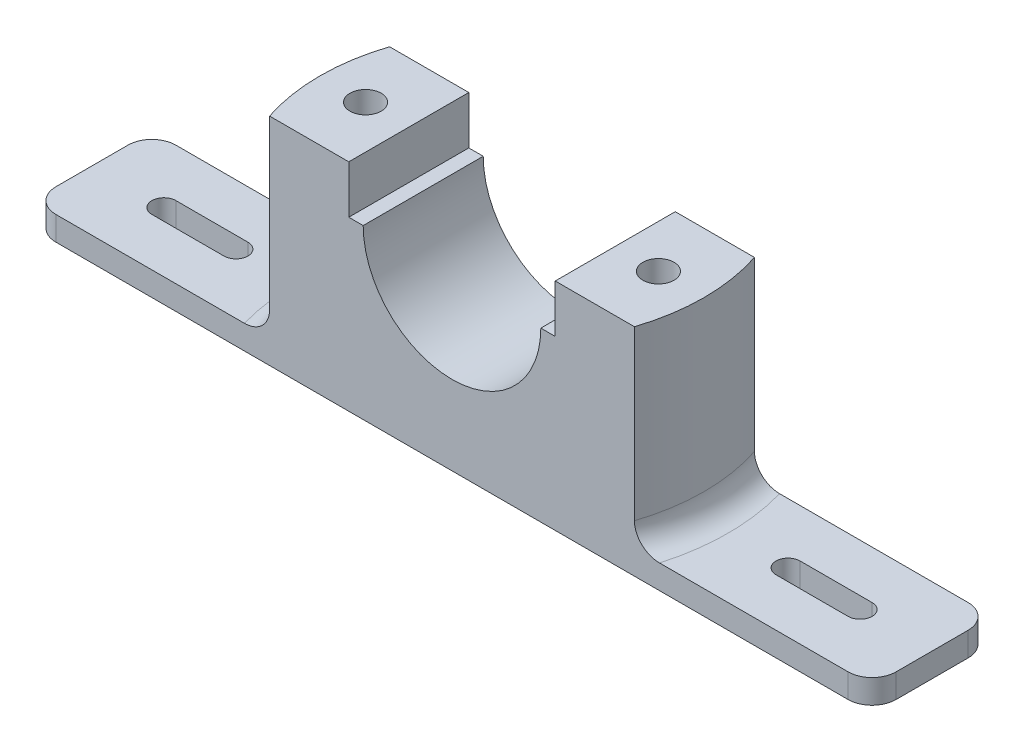
SolidWorks part; units mm, degrees
material "Plain Carbon Steel"
ref_plane "Front Plane" through (0, 0, 0) normal (0, 0, 1) x (1, 0, 0)
ref_plane "Top Plane" through (0, 0, 0) normal (0, 1, 0) x (1, 0, 0)
ref_plane "Right Plane" through (0, 0, 0) normal (1, 0, 0) x (0, 0, -1)
sketch "Sketch1" plane through (0, 0, 0) normal (0, 1, 0) x (1, 0, 0)
  line L2 (-87.5, 7.5) -> (-87.5, -7.5)
  line L5 (87.5, 7.5) -> (87.5, -7.5)
  line L7 (-82.5, 12.5) -> (82.5, 12.5)
  line L8 (82.5, -12.5) -> (-82.5, -12.5)
  line L9 (-72.5, 2.5) -> (-57.5, 2.5)
  line L10 (0, 12.5) -> (0, -12.5)
  line L11 (-72.5, -2.5) -> (-57.5, -2.5)
  line L12 (72.5, -2.5) -> (57.5, -2.5)
  line L13 (72.5, 2.5) -> (57.5, 2.5)
  line L14 (-22.5062, 12.5) -> (-22.5062, -12.5)
  line L15 (-22.5062, -12.5) -> (-19.7757, -12.5)
  line L16 (-19.7757, -12.5) -> (-19.7757, 12.5)
  line L17 (-19.7757, 12.5) -> (-22.5062, 12.5)
  line L18 (19.7757, -12.5) -> (19.7757, 12.5)
  line L19 (22.5062, -12.5) -> (19.7757, -12.5)
  line L20 (22.5062, 12.5) -> (22.5062, -12.5)
  line L21 (19.7757, 12.5) -> (22.5062, 12.5)
  arc A0 (-87.5, -7.5) -> (-82.5, -12.5) centre (-82.5, -7.5) ccw
  arc A1 (87.5, -7.5) -> (82.5, -12.5) centre (82.5, -7.5) cw
  arc A2 (82.5, 12.5) -> (87.5, 7.5) centre (82.5, 7.5) cw
  arc A3 (-82.5, 12.5) -> (-87.5, 7.5) centre (-82.5, 7.5) ccw
  arc A4 (-72.5, 2.5) -> (-72.5, -2.5) centre (-72.5, 0) ccw
  arc A5 (-57.5, -2.5) -> (-57.5, 2.5) centre (-57.5, 0) ccw
  arc A6 (72.5, 2.5) -> (72.5, -2.5) centre (72.5, 0) cw
  arc A7 (57.5, -2.5) -> (57.5, 2.5) centre (57.5, 0) cw
  circle A8 centre (-30.5, 0) radius 3.25
  arc A9 (-37.9967, 12.5) -> (-37.9967, -12.5) centre (0, 0) ccw
  arc A10 (-43.229, 12.5) -> (-43.229, -12.5) centre (0, 0) ccw
  circle A11 centre (30.5, 0) radius 3.25
  arc A12 (37.9967, 12.5) -> (37.9967, -12.5) centre (0, 0) cw
  arc A13 (43.229, 12.5) -> (43.229, -12.5) centre (0, 0) cw
  point P3 (-87.5, -12.5)
  point P13 (87.5, 12.5)
  point P16 (-87.5, 12.5)
  dimension "D4" = 5
  dimension "D12" = 6.5
  dimension "D13" = 57
  dimension "D14" = 40
  dimension "D15" = 45
  dimension "D16" = 12.5
  dimension "D1" = 25
  dimension "D2" = 12.5
  dimension "D3" = 175
  dimension "D5" = 10
  dimension "D6" = 15
  dimension "D7" = 15
  dimension "D8" = 15
  dimension "D9" = 10
  dimension "D10" = 15
extrude "Boss-Extrude5" add sketch "Sketch1" along normal blind 5 contours A10 L7 A3 L2 A0 L8 A5 L11 A4 L9 | L7 A10 L8 A9 | A13 L7 A12 L8 | L7 A13 L8 A1 L5 A2 L12 A7 L13 A6 region at (-85.676, 0, -10.676) region at (-41.8692, 0, 0) region at (41.8692, 0, 0) region at (62.8645, 0, -11.9916)
extrude "Boss-Extrude6" add sketch "Sketch1<8>" along normal blind 45 contours L7 A9 L8 L14 A8 | L16 L8 L10 L7 | L8 L18 L7 L10 | L20 L7 L18 L8 | A12 L7 L20 L8 A11 | L16 L17 L14 L15 region at (-30.2515, 0, -12.1949) region at (-9.8879, 0, 0) region at (9.8879, 0, 0) region at (21.141, 0, 0) region at (30.2515, 0, -12.1949)
sketch "Sketch1<8>" plane through (0, 0, 0) normal (0, 1, 0) x (1, 0, 0) same geometry as "Sketch1"
fillet "Fillet3" radius 5 1 edges at (-40, 5, 0) type face fillet first side face at (-38.9984, 25, 0) second side face at (-70.0113, 5, 0)
fillet "Fillet4" radius 5 1 edges at (40, 5, 0) type face fillet first side face at (38.9984, 25, 0) second side face at (70.0113, 5, 0)
sketch "Sketch4" plane through (0, 0, 12.5) normal (0, 0, 1) x (1, 0, 0)
  line L0 (-21.4967, 45) -> (-21.4967, 35)
  line L1 (37.9967, 45) -> (-37.9967, 45) construction
  line L2 (-21.4967, 35) -> (-18.4967, 35)
  line L3 (18.5033, 35) -> (21.5033, 35)
  line L4 (21.5033, 35) -> (21.5033, 45)
  line L5 (21.5033, 45) -> (-21.4967, 45)
  line L9 (-37.9967, 45) -> (-37.9967, 10) construction
  arc A0 (-18.4967, 35) -> (18.5033, 35) centre (0.0033, 35) ccw
  point P12 (0, 0)
  dimension "D5" = 38
  dimension "D1" = 18.5
  dimension "D2" = 10
  dimension "D3" = 3
  dimension "D4" = 3
extrude "Cut-Extrude1" cut sketch "Sketch4" against normal blind 45
